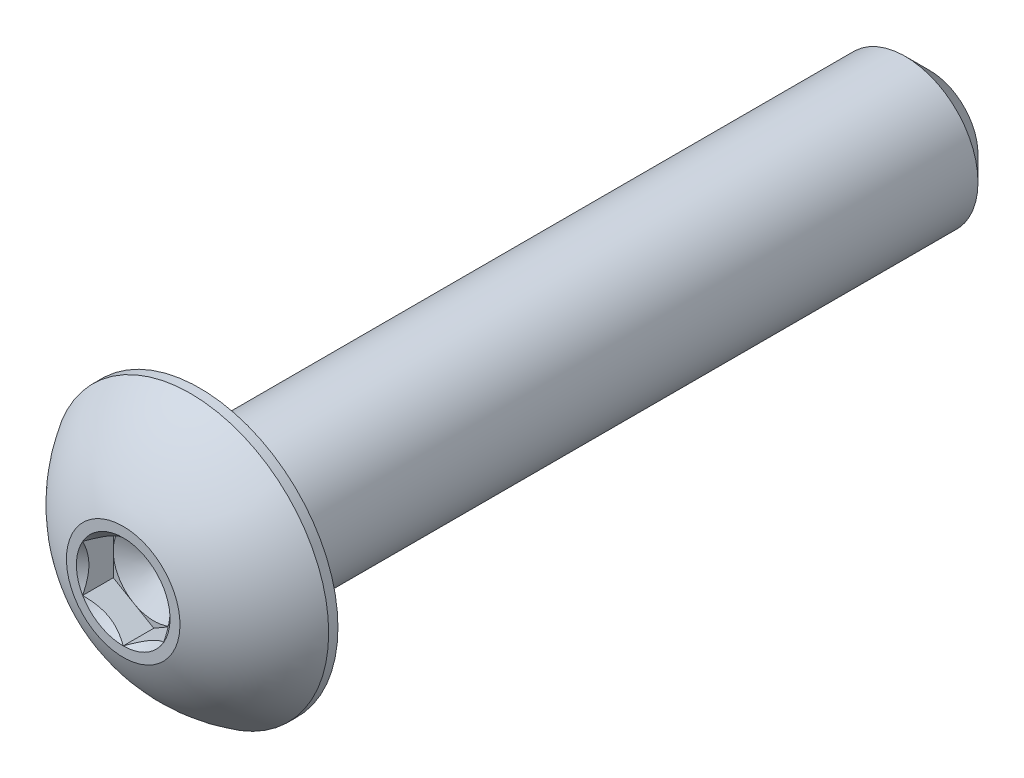
SolidWorks part; units mm, degrees
ref_plane "Front Plane" through (0, 0, 0) normal (0, 0, 1) x (1, 0, 0)
ref_plane "Top Plane" through (0, 0, 0) normal (0, 1, 0) x (1, 0, 0)
ref_plane "Right Plane" through (0, 0, 0) normal (1, 0, 0) x (0, 0, -1)
sketch "Sketch1" plane through (0, 0, 0) normal (1, 0, 0) x (0, 0, -1)
  line L0 (-7.893, 0) -> (7.893, 0) construction
  line L1 (-6.3944, 2.7051) -> (-6.3944, -2.7051) construction
  line L2 (-7.893, 0.7937) -> (-7.893, -0.7937) construction
  line L3 (7.893, 1.4224) -> (7.893, -1.4224) construction
  line L4 (7.8534, 1.4911) -> (8.1709, 0.9412) construction
  line L5 (8.1709, 0.9412) -> (8.4884, 1.4911) construction
  line L6 (8.4884, 1.4911) -> (7.8534, 1.4911) construction
  line L7 (8.1709, 1.4911) -> (8.1709, 1.4224) construction
  line L8 (8.1709, 0.9412) -> (8.1709, 1.01) construction
  line L9 (8.1312, 1.01) -> (8.2105, 1.01)
  line L10 (-7.893, 1.1113) -> (-7.893, -1.1113) construction
  line L11 (-6.3944, 2.7051) -> (-6.5759, 2.7051) construction
  line L12 (-7.893, 0.7937) -> (-7.2936, 0.7937) construction
  line L13 (-7.2936, 0.7937) -> (-6.8353, 0) construction
  point P5 (-6.3944, 0)
  point P10 (5.6705, -1.4224)
  dimension "Drive Size" = 1.5875
  dimension "Head Diameter" = 5.4102
  dimension "Head Height" = 1.4986
  dimension "Screw Size Decimal Equivalent" = 2.8448
  dimension "Length" = 14.2875
  dimension "D1" = 2.2225
  dimension "Pitch" = 0.635
  dimension "D2" = 0.0794
  dimension "D3" = 2.2225
  dimension "D4" = 0.1814
  dimension "D5" = 60
  dimension "D6" = 0.5994
sketch "Sketch2" plane through (0, 0, 0) normal (1, 0, 0) x (0, 0, -1)
  line L0 (-7.893, 0.7937) -> (-7.893, 1.1113)
  line L1 (-6.5759, 2.7051) -> (-6.3944, 2.7051)
  line L2 (-6.3944, 2.7051) -> (-6.3944, 1.4224)
  line L3 (-6.3944, 2.7051) -> (-6.3944, -2.7051) construction
  line L4 (-6.3944, 1.4224) -> (7.4168, 1.4224)
  line L5 (7.893, 0.9462) -> (7.893, 0)
  line L6 (-7.893, 0.7937) -> (-7.2936, 0.7937)
  line L7 (-7.2936, 0.7937) -> (-6.8353, 0)
  line L8 (7.893, 0) -> (-6.8353, 0)
  line L9 (7.4168, 1.4224) -> (7.893, 0.9462)
  line L10 (7.4168, -1.4224) -> (7.4168, 1.4224) construction
  arc A0 (-6.5759, 2.7051) -> (-7.893, 1.1113) centre (-4.9255, 0) ccw
  point P13 (7.893, 1.4224)
  point P25 (7.4168, 0)
  dimension "D1" = 0.4763
  dimension "D2" = 45
revolve "Revolve1" add sketch "Sketch2" angle 360 about L0
sketch "Sketch3" plane through (0, 0, 0) normal (0, 0, 1) x (1, 0, 0)
  line L1 (0, 0.9165) -> (-0.7938, 0.4583)
  line L2 (-0.7938, 0.4583) -> (-0.7937, -0.4583)
  line L3 (-0.7937, -0.4583) -> (0, -0.9165)
  line L4 (0, -0.9165) -> (0.7938, -0.4583)
  line L5 (0.7938, -0.4583) -> (0.7938, 0.4583)
  line L6 (0.7938, 0.4583) -> (0, 0.9165)
  circle A0 centre (0, 0) radius 0.7937 construction
extrude "Cut-Extrude1" cut sketch "Sketch3" along normal through all from vertex starting at point (0, 0.7937, 7.2936)
sketch "Sketch4" plane through (0, 0, 7.893) normal (0, 0, 1) x (1, 0, 0)
  circle A0 centre (0, 0) radius 0.9165
extrude "Cut-Extrude2" cut sketch "Sketch4" against normal up to next (15.7861 mm away) draft 45
sketch "Sketch9" plane through (0, 0, 0) normal (1, 0, 0) x (0, 0, -1)
  line L0 (7.893, -1.4224) -> (-6.3944, -1.4224) construction
  line L1 (-6.3944, -1.4224) -> (7.4168, -1.4224) construction
  line L2 (7.893, -0.9462) -> (7.893, 0.9462) construction
  line L3 (-6.3944, -1.4224) -> (-6.3944, 1.4224) construction
  point P9 (6.9405, -1.4224)
  dimension "D1" = 0.9525
sketch "Sketch5" plane through (0, 0, -7.893) normal (0, 0, -1) x (-1, 0, 0)
  circle A0 centre (0, 0) radius 1.4224
ref_axis "Center Axis1" through (0, 0, -89.0628) along (0, 0, 1)
ref_plane "Contact Plane1" through (0, 0, -7.893) normal (0, 0, 1) x (1, 0, 0)
ref_plane "Contact Plane2" through (0, 0, 6.3944) normal (0, 0, 1) x (1, 0, 0)
split "Split1" bodies to split 104 resulting bodies 109 110 split by face at (2.7051, 0, 6.3944)
curve "Helix/Spiral1" [suppressed] pitch 0.635 height 14.9225 turns 23.5
sketch "Sketch6" plane through (0, 0, 0) normal (1, 0, 0) x (0, 0, -1)
  line L0 (7.893, 1.4224) -> (8.4487, 1.4224)
  line L1 (8.4487, 1.4224) -> (8.2105, 1.01)
  line L2 (8.1312, 1.01) -> (8.2105, 1.01)
  line L3 (8.1312, 1.01) -> (7.893, 1.4224)
  line L4 (8.1709, 0.9412) -> (8.4884, 1.4911) construction
sweep "Cut-Sweep1" [suppressed] cut profiles "Sketch6" path "Helix/Spiral1"
sketch "Sketch10" plane through (0, 0, 6.3944) normal (0, 0, -1) x (-1, 0, 0)
  circle A0 centre (0, 0) radius 1.4295
  dimension "D1" = 2.859
extrude "Boss-Extrude1" add sketch "Sketch10" along normal through all draft 30
equation "\"D2@Sketch1\"=\"Pitch@Sketch1\"*.125"
equation "\"D1@Sketch1\"=\"Pitch@Sketch1\"*3.5"
equation "\"D3@Sketch1\"=\"Drive Size@Sketch1\"*1.4"
equation "\"D4@Sketch1\"=(\"D3@Sketch1\"-\"Drive Size@Sketch1\")/3.5"
equation "\"D6@Sketch1\"=\"Head Height@Sketch1\"*.40"
equation "\"D1@Sketch2\"=\"Pitch@Sketch1\"*.750"
equation "\"D4@Helix/Spiral1\"=\"Pitch@Sketch1\""
equation "\"D3@Helix/Spiral1\" = \"D4@Helix/Spiral1\" + \"Length@Sketch1\""
equation "\"D1@Sketch9\"=\"Pitch@Sketch1\"*1.5"
equation "\"D1@Sketch10\"=\"Screw Size Decimal Equivalent@Sketch1\"*1.005"
